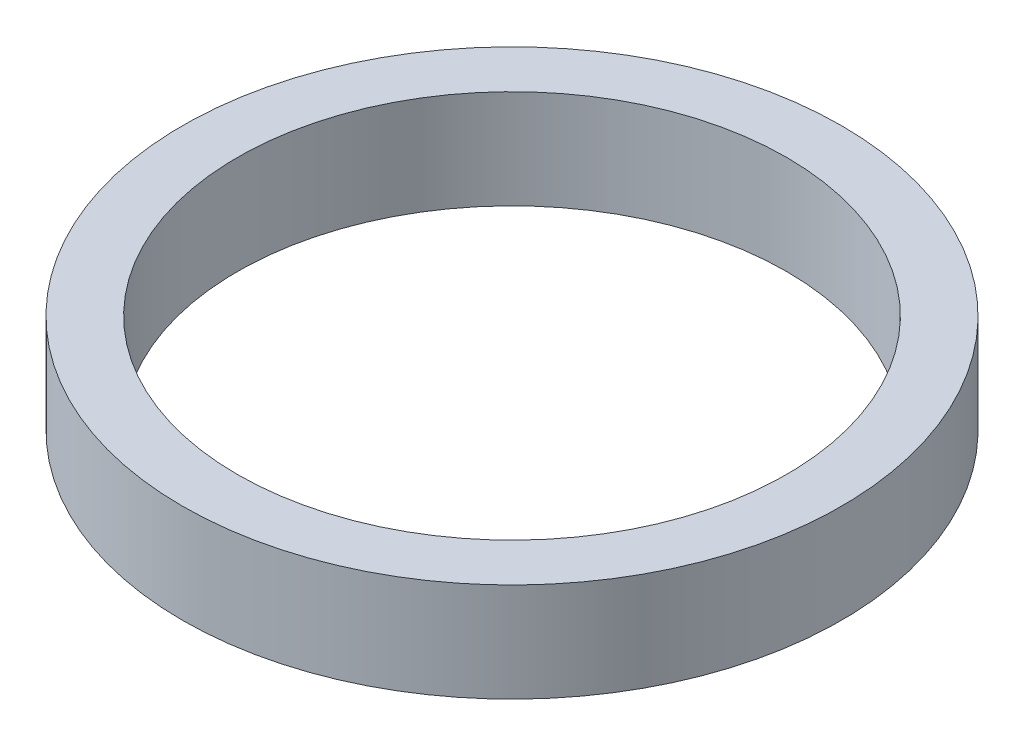
SolidWorks part; units mm, degrees
ref_plane "Front Plane" through (0, 0, 0) normal (0, 0, 1) x (1, 0, 0)
ref_plane "Top Plane" through (0, 0, 0) normal (0, 1, 0) x (1, 0, 0)
ref_plane "Right Plane" through (0, 0, 0) normal (1, 0, 0) x (0, 0, -1)
sketch "Sketch1" plane through (0, 0, 0) normal (0, 1, 0) x (1, 0, 0)
  circle A0 centre (0, 0) radius 60
  dimension "FLANGE_OD" = 120
extrude "Boss-Extrude1" add sketch "Sketch1" along normal blind 18
sketch "Sketch2" plane through (0, 0, 0) normal (0, 1, 0) x (1, 0, 0)
  circle A0 centre (0, 0) radius 50
  dimension "BORE_D" = 100
extrude "Cut-Extrude1" cut sketch "Sketch2" along normal through all
sketch "Sketch3" plane through (0, 18, 0) normal (0, 1, 0) x (1, 0, 0)
  circle A0 centre (0, 0) radius 27.5224 construction
  circle A1 centre (-27.5224, 0) radius 1.7112
  dimension "BOLT_D" = 3.4224
  dimension "BOLT_PCD" = 55.0448
extrude "Cut-Extrude2" cut sketch "Sketch3" against normal blind 13.8902 rebuild error yes
pattern_circular "CirPattern1" count 8 over 360 rebuild error yes
